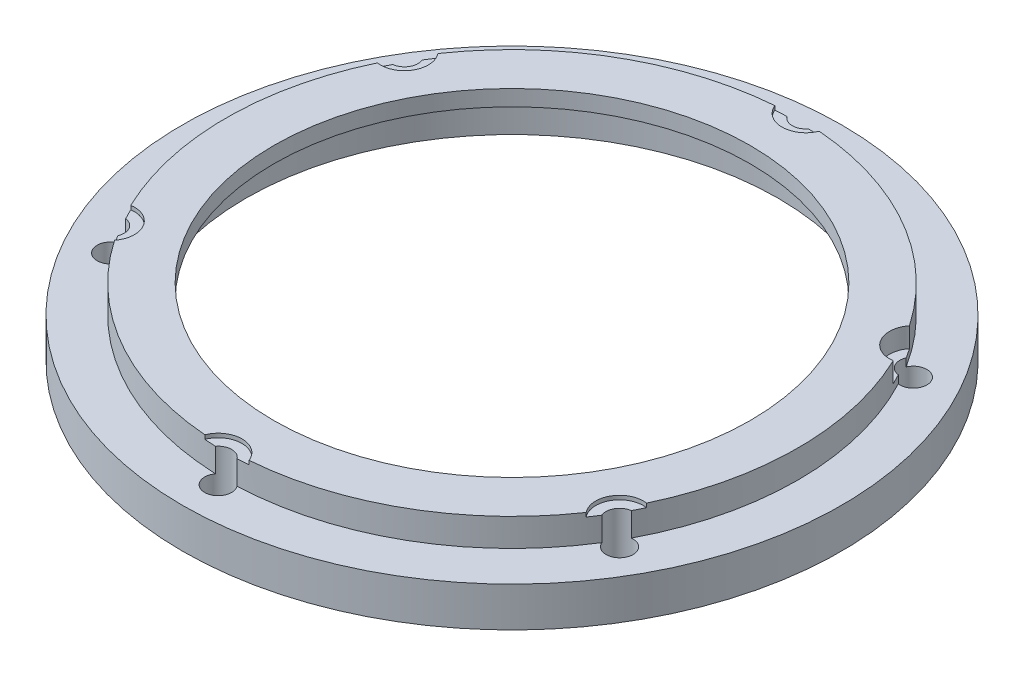
SolidWorks part; units mm, degrees
ref_plane "前视基准面" through (0, 0, 0) normal (0, 0, 1) x (1, 0, 0)
ref_plane "上视基准面" through (0, 0, 0) normal (0, 1, 0) x (1, 0, 0)
ref_plane "右视基准面" through (0, 0, 0) normal (1, 0, 0) x (0, 0, -1)
sketch "草图2" plane through (0, 0, 0) normal (1, 0, 0) x (0, 0, -1)
  line L9 (-30, 0) -> (-30, 2)
  line L10 (-30, 2) -> (-36, 2)
  line L11 (-30, 0) -> (-33.5, 0)
  line L12 (-33.5, 0) -> (-33.5, -5.5)
  line L13 (-33.5, -5.5) -> (-35, -5.5)
  line L14 (-35, -5.5) -> (-35, -6.5)
  line L15 (-35, -6.5) -> (-41.5, -6.5)
  line L16 (-36, 2) -> (-36, -1.5)
  line L17 (-36, -1.5) -> (-41.5, -1.5)
  line L18 (-41.5, -1.5) -> (-41.5, -6.5)
ref_axis "基准轴1" through (0, 0, 0) along (0, 1, 0)
revolve "旋转1" add sketch "草图2" angle 360 about axis through (0, 0, 0) along (0, 1, 0)
sketch "草图3" plane through (0, -1.5, 0) normal (0, 1, 0) x (1, 0, 0)
  circle A0 centre (0, 37) radius 1.7
  circle A1 centre (32.0429, 18.5) radius 1.7
  circle A2 centre (32.0429, -18.5) radius 1.7
  circle A3 centre (0, -37) radius 1.7
  circle A4 centre (-32.0429, -18.5) radius 1.7
  circle A5 centre (-32.0429, 18.5) radius 1.7
  point P16 (0, 0)
  dimension "D1" = 6
extrude "切除-拉伸1" cut sketch "草图3" against normal blind 10 and the other way up to next
sketch "草图4" plane through (0, -1.5, 0) normal (0, 1, 0) x (1, 0, 0)
  circle A0 centre (0, 37) radius 3
  circle A1 centre (32.0429, 18.5) radius 3
  circle A2 centre (32.0429, -18.5) radius 3
  circle A3 centre (0, -37) radius 3
  circle A4 centre (-32.0429, -18.5) radius 3
  circle A5 centre (-32.0429, 18.5) radius 3
  point P16 (0, 0)
  dimension "D1" = 6
extrude "切除-拉伸2" cut sketch "草图4" along normal blind 3 from offset 3
sketch "草图7" plane through (0, -1.5, 0) normal (0, 1, 0) x (1, 0, 0)
  circle A0 centre (32.0429, 18.5) radius 3
extrude "切除-拉伸3" cut sketch "草图7" along normal blind 10
sketch "草图8" plane through (0, -1.5, 0) normal (0, 1, 0) x (1, 0, 0)
  arc A1 (29.6894, 20.3603) -> (32.4772, 15.5316) centre (0, 0) cw
  arc A2 (29.6894, 20.3603) -> (32.4772, 15.5316) centre (32.0429, 18.5) ccw
  arc A3 (32.4772, -15.5316) -> (32.4772, 15.5316) centre (0, 0) ccw construction
  circle M2 centre (32.0429, 18.5) radius 1.7
  arc M4 (29.6894, 20.3603) -> (32.4772, 15.5316) centre (32.0429, 18.5) ccw
extrude "凸台-拉伸1" add sketch "草图8" along normal blind 1 contours A1 M4 M2 region at (30.3467, -1.5, -17.5207)
